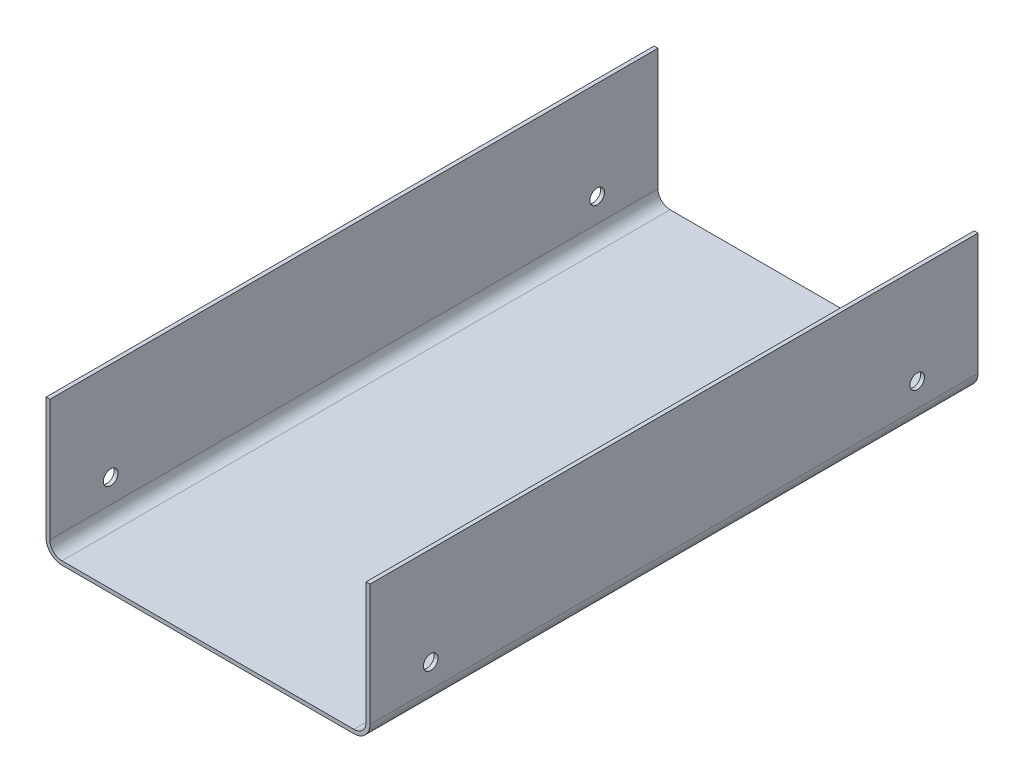
SolidWorks part; units mm, degrees
ref_plane "Front Plane" through (0, 0, 0) normal (0, 0, 1) x (1, 0, 0)
ref_plane "Top Plane" through (0, 0, 0) normal (0, 1, 0) x (1, 0, 0)
ref_plane "Right Plane" through (0, 0, 0) normal (1, 0, 0) x (0, 0, -1)
sketch "Sketch1" plane through (0, 0, 0) normal (0, 0, 1) x (1, 0, 0)
  line L8 (130, 110) -> (130, 0)
  line L9 (-130, 0) -> (130, 0)
  line L10 (-130, 0) -> (-130, 110)
  line L11 (133.18, 110) -> (133.18, -3.18)
  line L12 (-133.18, -3.18) -> (133.18, -3.18)
  line L13 (-133.18, -3.18) -> (-133.18, 110)
  line L14 (130, 110) -> (133.18, 110)
  line L15 (-130, 110) -> (-133.18, 110)
  point P5 (0, 0)
  dimension "D2" = 110
  dimension "D3" = 260
  dimension "D4" = 110
  dimension "D1" = 3.18
extrude "Boss-Extrude1" add sketch "Sketch1" along normal blind 500
fillet "Fillet2" radius 10 2 edges at (130, 0, 250) (-130, 0, 250)
fillet "Fillet3" radius 13.18 2 edges at (-133.18, -3.18, 250) (133.18, -3.18, 250)
sketch "Sketch2" plane through (133.18, 0, 0) normal (1, 0, 0) x (0, 0, -1)
  line L0 (-500, 10) -> (-500, 110) construction
  line L4 (0, 10) -> (0, 110) construction
  circle A0 centre (-450, 29.5) radius 6
  circle A1 centre (-50, 29.5) radius 6
  dimension "D3" = 12
  dimension "D4" = 12
  dimension "D1" = 50
  dimension "D2" = 29.5
  dimension "D5" = 50
  dimension "D6" = 29.5
extrude "Cut-Extrude1" cut sketch "Sketch2" against normal through all
equation "\"L\"= 500"
equation "\"W\"= 260"
equation "\"H\"= 110"
equation "\"Compartment Width\"= 100"
equation "\"T\"= 4.7625 * 2 / 3"
equation "\"D2@Sketch1\"= \"H\""
equation "\"D3@Sketch1\"= \"W\""
equation "\"D4@Sketch1\"= \"H\""
equation "\"D1@Boss-Extrude1\"= \"L\""
equation "\"D1@Sketch1\"=\"T\""
equation "\"Inside Fillet Radius\"= 10"
equation "\"D1@Fillet3\"=\"Inside Fillet Radius\"+\"T\""
